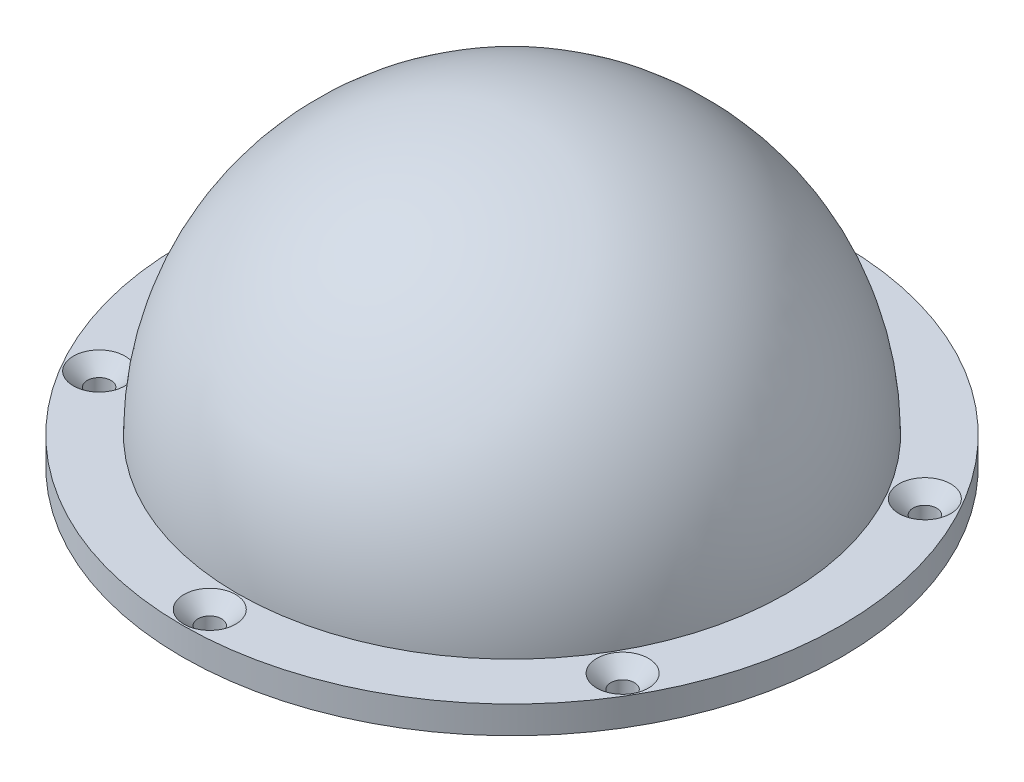
SolidWorks part; units mm, degrees
ref_plane "Спереди" through (0, 0, 0) normal (0, 0, 1) x (1, 0, 0)
ref_plane "Сверху" through (0, 0, 0) normal (0, 1, 0) x (1, 0, 0)
ref_plane "Справа" through (0, 0, 0) normal (1, 0, 0) x (0, 0, -1)
sketch "Эскиз1" plane through (0, 0, 0) normal (0, 0, 1) x (1, 0, 0)
  line L0 (0, 50) -> (0, 0) construction
  line L3 (0, -5) -> (60, -5)
  line L4 (60, 0) -> (60, -5)
  line L5 (0, 0) -> (50, 0) construction
  line L6 (50, 0) -> (60, 0)
  line L7 (0, 50) -> (0, -5)
  arc A0 (50, 0) -> (0, 50) centre (0, 0) ccw
  dimension "D1" = 50
  dimension "D2" = 60
  dimension "D3" = 5
revolve "Повернуть1" add sketch "Эскиз1" angle 360 about L7
hole_wizard "CSK for M4 Countersunk Flat Head Screw1" positions "Трехмерный эскиз1" profile "Эскиз2" countersink size "M4" standard "ISO" end condition through all
sketch3d "Трехмерный эскиз1"
  line L0 (0, 0, 0) -> (0, 0, -60) construction
  circle A0 centre (0, 0, 0) radius 60 construction
  point P0 (0, 0, -55)
  point P13 (0, 60, 0)
  dimension "D1" = 55
sketch "Эскиз2" plane through (0, 0, -55) normal (1, 0, 0) x (0, 0, 1)
  line L0 (0, 0) -> (0, 5)
  line L1 (0, 5) -> (2.15, 5)
  line L2 (2.15, 5) -> (2.15, 2.55)
  line L3 (2.15, 2.55) -> (4.7, 0)
  line L5 (4.7, 0) -> (0, 0)
  line L6 (-2.15, 2.55) -> (-4.7, 0) construction
  line L11 (0, -6.35) -> (0, 107.95) construction
  dimension "Диаметр сквозного отверстия" = 4.3
  dimension "Глубина сквозного отверстия" = 5
  dimension "Диаметр передней зенковки" = 9.4
  dimension "Угол передней зенковки" = 90
ref_axis "Ось1" through (0, 61.6031, 0) along (0, -1, 0)
pattern_circular "Круговой массив1" count 6 every 60 about axis through (0, 61.6031, 0) along (0, -1, 0) of "CSK for M4 Countersunk Flat Head Screw1"
